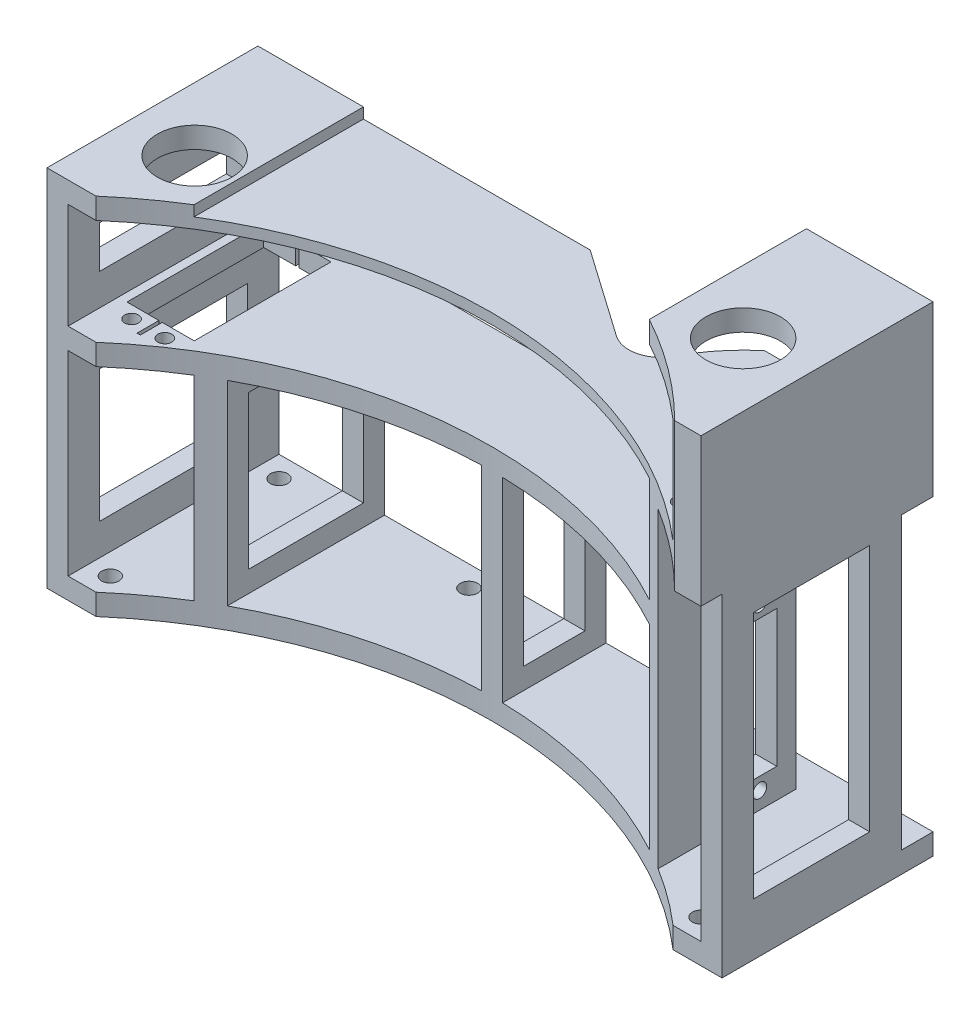
SolidWorks part; units mm, degrees
ref_plane "Front Plane" through (0, 0, 0) normal (0, 0, 1) x (1, 0, 0)
ref_plane "Top Plane" through (0, 0, 0) normal (0, 1, 0) x (1, 0, 0)
ref_plane "Right Plane" through (0, 0, 0) normal (1, 0, 0) x (0, 0, -1)
sketch "Sketch1" plane through (0, 0, 0) normal (0, 0, 1) x (1, 0, 0)
  line L0 (-101.6, 106.425) -> (101.6, 106.425)
  line L1 (-101.6, 0) -> (101.6, 0)
  line L2 (-101.6, 0) -> (-101.6, 106.425)
  line L4 (101.6, 0) -> (101.6, 106.425)
  point P5 (0, 0)
  dimension "D1" = 203.2
  dimension "D2" = 106.425
extrude "Boss-Extrude1" add sketch "Sketch1" along normal mid plane 63.5 contours L1 L4 L0 L2 | L0 region at (0, 53.2125, 0)
sketch "Sketch4" plane through (0, 0, -31.75) normal (0, 0, -1) x (-1, 0, 0)
  line L0 (-101.6, 0) -> (-101.6, 106.425) construction
  line L1 (101.6, 0) -> (101.6, 106.425) construction
  line L2 (-95.25, 103.25) -> (95.25, 103.25)
  line L3 (-95.25, 103.25) -> (-95.25, 71.5)
  line L4 (-95.25, 71.5) -> (95.25, 71.5)
  line L5 (95.25, 103.25) -> (95.25, 71.5)
  line L11 (-95.25, 65.15) -> (95.25, 65.15)
  line L12 (-95.25, 65.15) -> (-95.25, 6.35)
  line L13 (-95.25, 6.35) -> (95.25, 6.35)
  line L14 (95.25, 65.15) -> (95.25, 6.35)
  line L15 (101.6, 0) -> (-101.6, 0) construction
  dimension "D4" = 6.35
  dimension "D1" = 6.35
  dimension "D2" = 71.5
  dimension "D3" = 6.35
  dimension "D5" = 6.35
  dimension "D6" = 31.75
extrude "Cut-Extrude2" cut sketch "Sketch4" against normal through all
sketch "Sketch8" plane through (0, 0, 0) normal (0, 0, 1) x (1, 0, 0)
  line L0 (-95.25, 65.15) -> (95.25, 65.15) construction
  line L1 (-69.85, 65.15) -> (-63.5, 65.15)
  line L2 (-69.85, 65.15) -> (-69.85, 6.35)
  line L3 (-69.85, 6.35) -> (-63.5, 6.35)
  line L4 (-63.5, 65.15) -> (-63.5, 6.35)
  line L5 (95.25, 6.35) -> (-95.25, 6.35) construction
  line L6 (-95.25, 103.25) -> (95.25, 103.25) construction
  line L7 (63.5, 103.25) -> (69.85, 103.25)
  line L8 (63.5, 103.25) -> (63.5, 6.35)
  line L9 (63.5, 6.35) -> (69.85, 6.35)
  line L10 (69.85, 103.25) -> (69.85, 6.35)
  line L11 (95.25, 65.15) -> (95.25, 6.35) construction
  line L12 (-95.25, 6.35) -> (-95.25, 65.15) construction
  line L13 (-101.6, 0) -> (101.6, 0) construction
  line L14 (-3.175, 65.15) -> (3.175, 65.15)
  line L15 (-3.175, 65.15) -> (-3.175, 6.35)
  line L16 (-3.175, 6.35) -> (3.175, 6.35)
  line L17 (3.175, 65.15) -> (3.175, 6.35)
  point P24 (0, 0)
  point P25 (0, 6.35)
  dimension "D1" = 6.35
  dimension "D2" = 6.35
  dimension "D3" = 25.4
  dimension "D4" = 25.4
  dimension "D5" = 6.35
extrude "Boss-Extrude2" add sketch "Sketch8" along normal up to surface (31.75 mm away) from surface up to face at (0, 87.375, 31.75) starting at face at (0, 87.375, -31.75)
sketch "Sketch15" plane through (0, 103.25, 0) normal (0, -1, 0) x (1, 0, 0)
  line L4 (69.85, 31.75) -> (69.85, -31.75)
  line L5 (69.85, -31.75) -> (95.25, -31.75)
  line L6 (95.25, -31.75) -> (95.25, 31.75)
  line L7 (95.25, 31.75) -> (69.85, 31.75)
  line L8 (69.85, 31.75) -> (69.85, -31.75)
  line L9 (69.85, -31.75) -> (95.25, -31.75)
  line L10 (95.25, -31.75) -> (95.25, 31.75)
  line L11 (95.25, 31.75) -> (69.85, 31.75)
  dimension "D1" = 0
extrude "Boss-Extrude4" add sketch "Sketch15" along normal blind 3.175
sketch "Sketch2" plane through (0, 71.5, 0) normal (0, 1, 0) x (1, 0, 0)
  line L0 (-92.677, 24.55) -> (-72.423, -16.604) construction
  line L29 (-92.677, 24.55) -> (-83.05, 24.55)
  line L30 (-92.677, 24.55) -> (-92.677, -16.604)
  line L31 (-92.677, -16.604) -> (-83.05, -16.604)
  line L34 (-72.423, 24.55) -> (-72.423, -16.604)
  line L58 (69.85, 31.75) -> (69.85, -31.75)
  line L59 (69.85, -31.75) -> (95.25, -31.75)
  line L60 (95.25, -31.75) -> (95.25, 31.75)
  line L61 (95.25, 31.75) -> (69.85, 31.75)
  line L62 (69.85, 31.75) -> (69.85, -31.75)
  line L63 (69.85, -31.75) -> (95.25, -31.75)
  line L64 (95.25, -31.75) -> (95.25, 31.75)
  line L65 (95.25, 31.75) -> (69.85, 31.75)
  line L78 (-72.423, 24.55) -> (-92.677, -16.604) construction
  line L79 (-87.55, 28.273) -> (-77.55, -20.327) construction
  line L80 (-87.55, -20.327) -> (-77.55, 28.273) construction
  line L81 (-82.05, -16.604) -> (-72.423, -16.604)
  line L82 (-82.05, -16.604) -> (-82.05, -23.208)
  line L83 (-82.05, -23.208) -> (-83.05, -23.208)
  line L84 (-83.05, -16.604) -> (-83.05, -23.208)
  line L85 (-82.55, 3.973) -> (-13.3966, 3.973) construction
  line L86 (-82.05, 31.154) -> (-83.05, 31.154)
  line L87 (-82.05, 24.55) -> (-82.05, 31.154)
  line L88 (-83.05, 24.55) -> (-83.05, 31.154)
  line L89 (-82.05, 24.55) -> (-72.423, 24.55)
  line L90 (-101.6, -31.75) -> (101.6, -31.75) construction
  line L91 (-101.6, -31.75) -> (-101.6, 31.75) construction
  circle A12 centre (-87.55, -20.327) radius 2.1
  circle A13 centre (-77.55, -20.327) radius 2.1
  circle A14 centre (-87.55, 28.273) radius 2.1
  circle A15 centre (-77.55, 28.273) radius 2.1
  point P8 (-82.55, -23.208)
  point P17 (-82.55, 3.973)
  point P18 (-82.55, 3.973)
  point P27 (-82.55, -6.35)
  dimension "D3" = 48.6
  dimension "D4" = 4.2
  dimension "D2" = 10
  dimension "D5" = 41.154
  dimension "D6" = 20.254
  dimension "D7" = 1
  dimension "D8" = 6.604
  dimension "D9" = 30.9
  dimension "D10" = 25.4
  dimension "D11" = 0
  dimension "D12" = 19.05
extrude "Cut-Extrude3" cut sketch "Sketch2" against normal up to next
sketch "Sketch9" plane through (0, 106.425, 0) normal (0, 1, 0) x (1, 0, 0)
  line L0 (72.423, 24.55) -> (92.677, -16.604) construction
  line L1 (72.423, 24.55) -> (82.05, 24.55)
  line L2 (72.423, 24.55) -> (72.423, -16.604)
  line L3 (72.423, -16.604) -> (82.05, -16.604)
  line L4 (92.677, 24.55) -> (92.677, -16.604)
  line L5 (92.677, 24.55) -> (72.423, -16.604) construction
  line L6 (77.55, 28.273) -> (87.55, -20.327) construction
  line L7 (77.55, -20.327) -> (87.55, 28.273) construction
  line L8 (83.05, -16.604) -> (92.677, -16.604)
  line L9 (83.05, -16.604) -> (83.05, -23.208)
  line L10 (83.05, -23.208) -> (82.05, -23.208)
  line L11 (82.05, -16.604) -> (82.05, -23.208)
  line L12 (82.55, 3.973) -> (164.4034, 3.973) construction
  line L13 (83.05, 31.154) -> (82.05, 31.154)
  line L14 (83.05, 24.55) -> (83.05, 31.154)
  line L15 (82.05, 24.55) -> (82.05, 31.154)
  line L16 (83.05, 24.55) -> (92.677, 24.55)
  line L17 (101.6, -31.75) -> (101.6, 31.75) construction
  line L19 (-101.6, -31.75) -> (101.6, -31.75) construction
  circle A0 centre (77.55, -20.327) radius 2.1
  circle A1 centre (87.55, -20.327) radius 2.1
  circle A2 centre (77.55, 28.273) radius 2.1
  circle A3 centre (87.55, 28.273) radius 2.1
  point P8 (82.55, -23.208)
  point P17 (82.55, 3.973)
  point P18 (82.55, 3.973)
  point P27 (82.55, -6.35)
  dimension "D3" = 4.2
  dimension "D1" = 10
  dimension "D2" = 48.6
  dimension "D4" = 41.154
  dimension "D5" = 20.254
  dimension "D6" = 1
  dimension "D7" = 6.604
  dimension "D8" = 30.9
  dimension "D9" = 19.05
  dimension "D10" = 25.4
extrude "Cut-Extrude4" cut sketch "Sketch9" against normal up to next
sketch "Sketch12" plane through (0, 0, 0) normal (0, 1, 0) x (1, 0, 0)
  line L0 (-63.5, -31.75) -> (-63.5, 31.75) construction
  line L1 (-69.85, -31.75) -> (-95.25, -31.75) construction
  line L2 (-95.25, -31.75) -> (-95.25, 31.75) construction
  line L3 (-101.6, 31.75) -> (101.6, 31.75) construction
  circle A0 centre (-88.9, 25.4) radius 2.6
  circle A1 centre (-88.9, -25.4) radius 2.6
  circle A2 centre (-31.75, 25.4) radius 2.6
  dimension "D1" = 5.2
  dimension "D2" = 6.35
  dimension "D3" = 6.35
  dimension "D4" = 6.35
  dimension "D5" = 31.75
extrude "Cut-Extrude7" cut sketch "Sketch12" along normal up to surface (6.35 mm away) and the other way through all up to face at (-33.3375, 6.35, 0)
mirror "Mirror1" about plane through (0, 0, 0) normal (1, 0, 0) of "Cut-Extrude7"
sketch "Sketch16" plane through (0, 106.425, 0) normal (0, 1, 0) x (1, 0, 0)
  line L2 (-69.85, 31.75) -> (-101.6, 31.75)
  line L3 (-101.6, 31.75) -> (-101.6, -31.75)
  line L12 (-101.6, -31.75) -> (-69.85, -31.75)
  line L13 (-69.85, 31.75) -> (-69.85, -31.75)
  dimension "D1" = 31.75
extrude "Boss-Extrude5" add sketch "Sketch16" along normal blind 3.175
sketch "Sketch17" plane through (0, 109.6, 0) normal (0, 1, 0) x (1, 0, 0)
  line L0 (-101.6, -31.75) -> (-69.85, -31.75) construction
  line L1 (-101.6, 31.75) -> (-101.6, -31.75) construction
  circle A0 centre (-82.55, -6.35) radius 11.2395
  dimension "D3" = 22.479
  dimension "D1" = 25.4
  dimension "D2" = 19.05
extrude "Cut-Extrude8" cut sketch "Sketch17" against normal up to next
sketch "Sketch18" plane through (0, 106.425, 0) normal (0, 1, 0) x (1, 0, 0)
  line L5 (101.6, -31.75) -> (101.6, 31.75) construction
  line L6 (-69.85, -31.75) -> (101.6, -31.75) construction
  line L14 (101.6, -31.75) -> (101.6, 31.75)
  line L15 (101.6, 31.75) -> (95.25, 31.75)
  line L16 (95.25, -31.75) -> (95.25, 31.75)
  line L22 (95.25, -31.75) -> (82.55, -31.75)
  line L23 (101.6, -31.75) -> (101.6, -38.1)
  line L24 (101.6, -38.1) -> (82.55, -38.1)
  line L25 (82.55, -31.75) -> (82.55, -38.1)
  dimension "D4" = 6.35
  dimension "D5" = 19.05
extrude "Boss-Extrude6" add sketch "Sketch18" along normal blind 38.1 from surface starting at face at (87.55, 100.075, 18.227)
sketch "Sketch20" plane through (0, 138.175, 0) normal (0, 1, 0) x (1, 0, 0)
  line L1 (63.5, 31.75) -> (101.6, 31.75)
  line L2 (63.5, 31.75) -> (63.5, -38.1)
  line L3 (63.5, -38.1) -> (101.6, -38.1)
  line L4 (101.6, 31.75) -> (101.6, -38.1)
  line L6 (-69.85, -31.75) -> (82.55, -31.75) construction
  circle A0 centre (82.55, -6.35) radius 11.2395
  dimension "D2" = 19.05
  dimension "D1" = 22.479
  dimension "D4" = 38.1
  dimension "D3" = 25.4
extrude "Boss-Extrude7" add sketch "Sketch20" along normal blind 6.35
sketch "Sketch10" plane through (0, 106.425, 0) normal (0, 1, 0) x (1, 0, 0)
  circle A3 centre (0, -132.08) radius 131.1117 construction
  circle A4 centre (0, -132.08) radius 131.1117 construction
  circle A5 centre (0, -132.08) radius 132.6992
  dimension "D1" = 1.5875
extrude "Cut-Extrude5" cut sketch "Sketch10" against normal through all both and the other way through all
sketch "Sketch21" plane through (0, 106.425, 0) normal (0, 1, 0) x (1, 0, 0)
  line L5 (34.6759, 6.35) -> (-1.5991, 31.75)
  line L6 (-69.85, 31.75) -> (95.25, 31.75) construction
  line L7 (-1.5991, 31.75) -> (50.9018, 31.75)
  arc A1 (34.6759, 6.35) -> (50.9018, 31.75) centre (82.55, -6.35) cw
  dimension "D2" = 49.53
  dimension "D1" = 35
  dimension "D3" = 25.4
extrude "Cut-Extrude10" cut sketch "Sketch21" against normal up to surface (3.175 mm away) up to face at (-82.55, 103.25, 17.5895)
sketch "Sketch23" plane through (0, 0, -31.75) normal (0, 0, -1) x (-1, 0, 0)
  line L1 (-101.6, 6.35) -> (-57.15, 6.35)
  line L2 (-101.6, 6.35) -> (-101.6, 93.725)
  line L3 (-101.6, 93.725) -> (-57.15, 93.725)
  line L4 (-57.15, 6.35) -> (-57.15, 93.725)
  line L7 (-63.5, 71.5) -> (95.25, 71.5) construction
  line L9 (-63.5, 65.15) -> (-63.5, 6.35) construction
  line L10 (-101.6, 0) -> (-101.6, 144.525) construction
  line L11 (-63.5, 6.35) -> (-3.175, 6.35) construction
  dimension "D1" = 6.35
  dimension "D2" = 22.225
extrude "Cut-Extrude11" cut sketch "Sketch23" against normal blind 9.525
sketch "Sketch24" plane through (63.5, 0, 0) normal (-1, 0, 0) x (0, 0, 1)
  line L0 (-16.477, 56.354) -> (3.777, 15.2) construction
  line L1 (-16.477, 56.354) -> (-6.85, 56.354)
  line L2 (-16.477, 56.354) -> (-16.477, 15.2)
  line L3 (-16.477, 15.2) -> (-6.85, 15.2)
  line L4 (3.777, 56.354) -> (3.777, 15.2)
  line L5 (3.777, 56.354) -> (-16.477, 15.2) construction
  line L6 (-11.35, 60.077) -> (-1.35, 11.477) construction
  line L7 (-11.35, 11.477) -> (-1.35, 60.077) construction
  line L8 (-5.85, 15.2) -> (3.777, 15.2)
  line L9 (-5.85, 15.2) -> (-5.85, 8.596)
  line L10 (-5.85, 8.596) -> (-6.85, 8.596)
  line L11 (-6.85, 15.2) -> (-6.85, 8.596)
  line L12 (-6.35, 35.777) -> (65.4757, 35.777) construction
  line L13 (-5.85, 62.958) -> (-6.85, 62.958)
  line L14 (-5.85, 56.354) -> (-5.85, 62.958)
  line L15 (-6.85, 56.354) -> (-6.85, 62.958)
  line L16 (-5.85, 56.354) -> (3.777, 56.354)
  line L17 (-22.225, 65.15) -> (-22.225, 6.35) construction
  line L18 (15.5603, 65.15) -> (-22.225, 65.15) construction
  circle A0 centre (-11.35, 11.477) radius 2.1
  circle A1 centre (-1.35, 11.477) radius 2.1
  circle A2 centre (-11.35, 60.077) radius 2.1
  circle A3 centre (-1.35, 60.077) radius 2.1
  point P8 (-6.35, 8.596)
  point P17 (-6.35, 35.777)
  point P18 (-6.35, 35.777)
  point P27 (-6.35, 46.1)
  dimension "D3" = 4.2
  dimension "D1" = 10
  dimension "D2" = 48.6
  dimension "D4" = 41.154
  dimension "D5" = 20.254
  dimension "D6" = 1
  dimension "D7" = 6.604
  dimension "D8" = 30.9
  dimension "D9" = 15.875
  dimension "D10" = 19.05
extrude "Cut-Extrude12" cut sketch "Sketch24" against normal up to next
sketch "Sketch26" plane through (95.25, 0, 0) normal (-1, 0, 0) x (0, 0, 1)
  line L12 (-12.7, 90.55) -> (-12.7, 15.875)
  line L13 (-12.7, 15.875) -> (22.225, 15.875)
  line L14 (22.225, 15.875) -> (22.225, 90.55)
  line L15 (22.225, 90.55) -> (-12.7, 90.55)
  line L16 (-12.7, 90.55) -> (-12.7, 15.875)
  line L17 (-12.7, 15.875) -> (22.225, 15.875)
  line L18 (22.225, 15.875) -> (22.225, 90.55)
  line L19 (22.225, 90.55) -> (-12.7, 90.55)
  dimension "D1" = 9.525
extrude "Cut-Extrude13" cut sketch "Sketch26" against normal up to next
sketch "Sketch27" plane through (63.5, 0, 0) normal (-1, 0, 0) x (0, 0, 1)
  line L6 (9.2103, 77.85) -> (9.2103, 96.9)
  line L8 (9.2103, 77.85) -> (9.2103, 96.9)
  line L12 (-15.875, 96.9) -> (-15.875, 77.85)
  line L13 (-15.875, 77.85) -> (9.2103, 77.85)
  line L15 (9.2103, 96.9) -> (-15.875, 96.9)
  line L16 (-15.875, 96.9) -> (-15.875, 77.85)
  line L17 (-15.875, 77.85) -> (9.2103, 77.85)
  line L19 (9.2103, 96.9) -> (-15.875, 96.9)
  dimension "D1" = 6.35
extrude "Cut-Extrude14" cut sketch "Sketch27" against normal up to next
sketch "Sketch28" plane through (3.175, 0, 0) normal (1, 0, 0) x (0, 0, -1)
  line L8 (25.4, 58.8) -> (6.9313, 58.8)
  line L9 (6.9313, 58.8) -> (6.9313, 12.7)
  line L10 (6.9313, 12.7) -> (25.4, 12.7)
  line L11 (25.4, 12.7) -> (25.4, 58.8)
  line L12 (25.4, 58.8) -> (6.9313, 58.8)
  line L13 (6.9313, 58.8) -> (6.9313, 12.7)
  line L14 (6.9313, 12.7) -> (25.4, 12.7)
  line L15 (25.4, 12.7) -> (25.4, 58.8)
  dimension "D1" = 6.35
extrude "Cut-Extrude15" cut sketch "Sketch28" against normal up to next
sketch "Sketch29" plane through (-63.5, 0, 0) normal (1, 0, 0) x (0, 0, -1)
  line L8 (25.4, 58.8) -> (-9.2103, 58.8)
  line L9 (-9.2103, 58.8) -> (-9.2103, 12.7)
  line L10 (-9.2103, 12.7) -> (25.4, 12.7)
  line L11 (25.4, 12.7) -> (25.4, 58.8)
  line L12 (25.4, 58.8) -> (-9.2103, 58.8)
  line L13 (-9.2103, 58.8) -> (-9.2103, 12.7)
  line L14 (-9.2103, 12.7) -> (25.4, 12.7)
  line L15 (25.4, 12.7) -> (25.4, 58.8)
  dimension "D1" = 6.35
extrude "Cut-Extrude16" cut sketch "Sketch29" against normal up to next
sketch "Sketch30" plane through (-95.25, 0, 0) normal (1, 0, 0) x (0, 0, -1)
  line L8 (22.225, 15.875) -> (22.225, 55.625)
  line L9 (22.225, 55.625) -> (-22.225, 55.625)
  line L10 (-22.225, 55.625) -> (-22.225, 15.875)
  line L11 (-22.225, 15.875) -> (22.225, 15.875)
  line L12 (22.225, 15.875) -> (22.225, 55.625)
  line L13 (22.225, 55.625) -> (-22.225, 55.625)
  line L14 (-22.225, 55.625) -> (-22.225, 15.875)
  line L15 (-22.225, 15.875) -> (22.225, 15.875)
  dimension "D1" = 9.525
extrude "Cut-Extrude17" cut sketch "Sketch30" against normal up to next
sketch "Sketch31" plane through (-95.25, 0, 0) normal (1, 0, 0) x (0, 0, -1)
  line L4 (22.225, 81.025) -> (22.225, 93.725)
  line L6 (22.225, 81.025) -> (22.225, 93.725)
  line L9 (22.225, 93.725) -> (-22.225, 93.725)
  line L10 (-22.225, 93.725) -> (-22.225, 81.025)
  line L11 (-22.225, 81.025) -> (22.225, 81.025)
  line L13 (22.225, 93.725) -> (-22.225, 93.725)
  line L14 (-22.225, 93.725) -> (-22.225, 81.025)
  line L15 (-22.225, 81.025) -> (22.225, 81.025)
  dimension "D1" = 9.525
extrude "Cut-Extrude18" cut sketch "Sketch31" against normal up to next
fillet "Fillet1" radius 9.525 1 edges at (34.6759, 104.8375, -6.35)
equation "\"tightTol\"= 0.005in"
equation "\"normTol\"= 0.01in"
equation "\"looseTol\"= 0.02in"
equation "\"D1@Sketch12\"=5.2mm"
equation "\"D2@Sketch1\"=8mm+0.5+3.25+0.125"
equation "\"D2@Sketch4\"=8mm+0.25+2.25"
equation "\"D3@Sketch17\" = 7 / 8 + \"normTol\""
equation "\"D1@Sketch20\"=7/8+\"normTol\""
